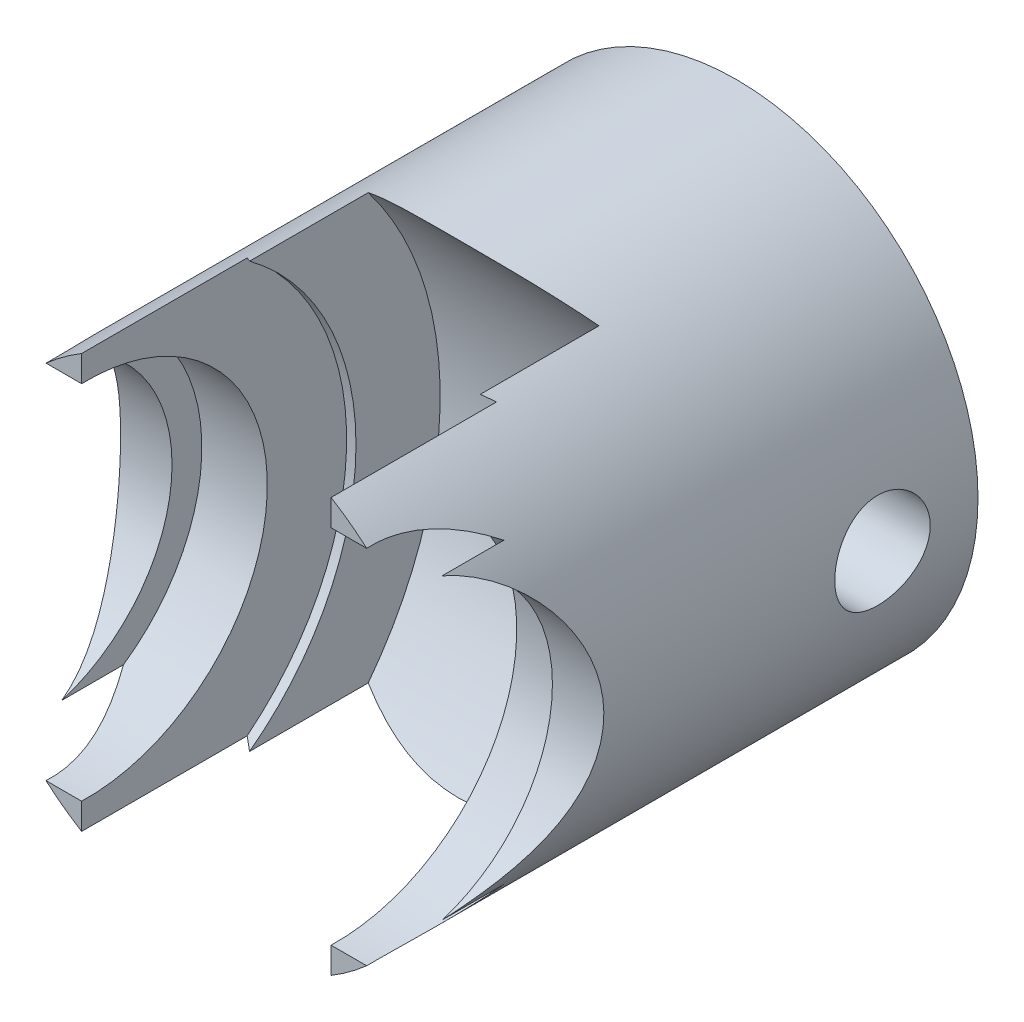
SolidWorks part; units mm, degrees
material "Hexcel AS4C (3000 Filaments)"
ref_plane "Front" through (0, 0, 0) normal (0, 0, 1) x (1, 0, 0)
ref_plane "Top" through (0, 0, 0) normal (0, 1, 0) x (1, 0, 0)
ref_plane "Right" through (0, 0, 0) normal (1, 0, 0) x (0, 0, -1)
sketch "Sketch1" plane through (0, 0, 0) normal (0, 0, 1) x (1, 0, 0)
  circle A0 centre (0, 0) radius 7.75
extrude "Extrude1" add sketch "Sketch1" along normal blind 17
sketch "Sketch2" plane through (0, 0, 0) normal (1, 0, 0) x (0, 0, -1)
  line L1 (-17, 7.75) -> (-17, -7.75) construction
  line L2 (-17, 7.75) -> (-3.5707, 7.75) construction
  line L4 (-17, 7.75) -> (-17, -7.8198)
  line L5 (-16.9284, -7.8198) -> (-3.2191, -7.8198) construction
  line L6 (-17, 7.75) -> (-8.9144, 7.75)
  line L7 (-17, -7.8198) -> (-8.9819, -7.8198)
  circle A0 centre (-17, 0) radius 11.2 construction
  arc A1 (-8.9144, 7.75) -> (-8.9819, -7.8198) centre (-17, 0) cw
extrude "Extrude2" cut sketch "Sketch2" against normal blind 3.7 and the other way blind 3.7
sketch "Sketch3" plane through (0, 0, 0) normal (1, 0, 0) x (0, 0, -1)
  line L0 (-17, 6.8097) -> (-17, -6.8097) construction
  circle A0 centre (-17, 0) radius 8.5
extrude "Extrude3" cut sketch "Sketch3" against normal blind 4 and the other way blind 4
sketch "Sketch4" plane through (0, 0, 0) normal (1, 0, 0) x (0, 0, -1)
  line L0 (-17, 6.638) -> (-17, -6.638) construction
  line L1 (-3.0625, 9.1875) -> (-3.0625, -9.1875) construction
  circle A0 centre (-17, 0) radius 5
  circle A1 centre (-3.0625, 0) radius 1.5312
  dimension "D1" = 13.9375
extrude "Extrude4" cut sketch "Sketch4" against normal through all and the other way through all
sketch "Sketch5" plane through (0, 0, 0) normal (1, 0, 0) x (0, 0, -1)
  circle A0 centre (-16.8438, 0) radius 5.8
extrude "Extrude5" cut sketch "Sketch5" against normal blind 6.1 and the other way blind 6.1
